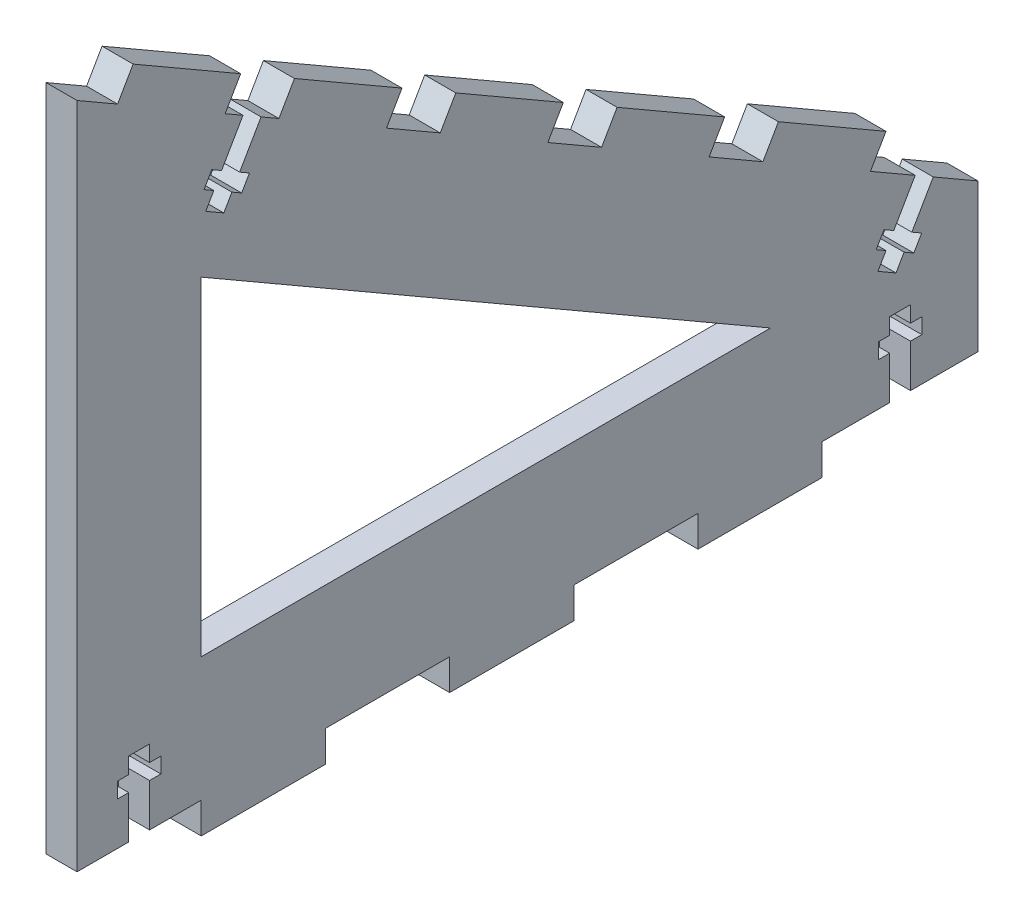
SolidWorks part; units mm, degrees
ref_plane "Front Plane" through (0, 0, 0) normal (0, 0, 1) x (1, 0, 0)
ref_plane "Top Plane" through (0, 0, 0) normal (0, 1, 0) x (1, 0, 0)
ref_plane "Right Plane" through (0, 0, 0) normal (1, 0, 0) x (0, 0, -1)
sketch "Sketch1" plane through (-32.0384, 0, 0) normal (-1, 0, 0) x (0, 0, 1)
  line L0 (-213.5096, 95.25) -> (-213.5096, 125.4926)
  line L1 (165.3114, 95.25) -> (-69.85, 95.25) construction
  line L2 (-213.5096, 125.4926) -> (-29.2385, 231.8816)
  line L3 (-29.2385, 231.8816) -> (-29.2385, 95.25)
  line L4 (-29.2385, 95.25) -> (-213.5096, 95.25)
  line L5 (-29.2385, 231.8816) -> (-42.2787, 224.3528) construction
  line L6 (-29.2385, 95.25) -> (-29.2385, 231.8816) construction
extrude "Boss-Extrude1" add sketch "Sketch1" along normal mid plane 6.35
sketch "Sketch2" plane through (-35.2134, 0, 0) normal (-1, 0, 0) x (0, 0, 1)
  line L14 (-54.6385, 120.65) -> (-54.6385, 187.8875)
  line L15 (-171.0972, 120.65) -> (-54.6385, 120.65)
  line L16 (-54.6385, 187.8875) -> (-171.0972, 120.65)
  line L17 (-54.6385, 120.65) -> (-54.6385, 187.8875)
  line L18 (-171.0972, 120.65) -> (-54.6385, 120.65)
  line L19 (-54.6385, 187.8875) -> (-171.0972, 120.65)
  dimension "D1" = 25.4
extrude "Cut-Extrude1" cut sketch "Sketch2" against normal blind 6.35
sketch "Sketch3" plane through (0, 186.5718, -107.7173) normal (0, 0.866, -0.5) x (1, 0, 0)
  line L0 (-35.2134, -90.6195) -> (-35.2134, 122.1584) construction
  line L1 (-35.2134, 96.7584) -> (-28.8634, 96.7584)
  line L2 (-35.2134, 96.7584) -> (-35.2134, 71.3584)
  line L3 (-35.2134, 71.3584) -> (-28.8634, 71.3584)
  line L4 (-28.8634, 96.7584) -> (-28.8634, 71.3584)
  line L5 (-28.8634, -90.6195) -> (-28.8634, 122.1584) construction
  dimension "D1" = 25.4
  dimension "D2" = 25.4
extrude "Boss-Extrude2" add sketch "Sketch3" along normal blind 6.35
pattern_linear "LPattern1" count 5 spacing 38.1 along (0, 0.5, 0.866) of "Boss-Extrude2"
sketch "Sketch4" plane through (0, 95.25, 0) normal (0, -1, 0) x (1, 0, 0)
  line L0 (-35.2134, -213.5096) -> (-35.2134, -29.2385) construction
  line L1 (-35.2134, -54.6385) -> (-28.8634, -54.6385)
  line L2 (-35.2134, -54.6385) -> (-35.2134, -80.0385)
  line L3 (-35.2134, -80.0385) -> (-28.8634, -80.0385)
  line L4 (-28.8634, -54.6385) -> (-28.8634, -80.0385)
  line L5 (-28.8634, -213.5096) -> (-28.8634, -29.2385) construction
  dimension "D1" = 25.4
  dimension "D2" = 25.4
extrude "Boss-Extrude3" add sketch "Sketch4" along normal blind 6.35
pattern_linear "LPattern2" count 3 spacing 50.8 along (0, 0, -1) of "Boss-Extrude3"
sketch "Sketch5" plane through (-28.8634, 0, 0) normal (1, 0, 0) x (0, 0, -1)
  line L0 (215.9, 95.25) -> (-165.3114, 95.25) construction
  line L1 (197.5741, 95.25) -> (197.5741, 119.6237) construction
  line L2 (213.5096, 95.25) -> (181.6385, 95.25) construction
  line L3 (41.9385, 95.25) -> (41.9385, 127.2639) construction
  line L4 (54.6385, 95.25) -> (29.2385, 95.25) construction
  line L5 (69.85, 95.25) -> (-165.3114, 95.25) construction
  line B0 (195.4405, 95.25) -> (199.7077, 95.25)
  line B1 (199.7077, 107.188) -> (202.0191, 107.188)
  line B2 (202.0191, 107.188) -> (202.0191, 104.013)
  line B3 (202.0191, 104.013) -> (199.7077, 104.013)
  line B4 (199.7077, 104.013) -> (199.7077, 95.25)
  line B5 (199.7077, 107.188) -> (199.7077, 110.49)
  line B6 (199.7077, 110.49) -> (195.4405, 110.49)
  line B7 (195.4405, 107.188) -> (195.4405, 110.49)
  line B8 (195.4405, 104.013) -> (195.4405, 95.25)
  line B9 (193.1291, 104.013) -> (195.4405, 104.013)
  line B10 (193.1291, 107.188) -> (193.1291, 104.013)
  line B11 (195.4405, 107.188) -> (193.1291, 107.188)
  line B12 (39.8049, 95.25) -> (44.0721, 95.25)
  line B13 (44.0721, 107.188) -> (46.3835, 107.188)
  line B14 (46.3835, 107.188) -> (46.3835, 104.013)
  line B15 (46.3835, 104.013) -> (44.0721, 104.013)
  line B16 (44.0721, 104.013) -> (44.0721, 95.25)
  line B17 (44.0721, 107.188) -> (44.0721, 110.49)
  line B18 (44.0721, 110.49) -> (39.8049, 110.49)
  line B19 (39.8049, 107.188) -> (39.8049, 110.49)
  line B20 (39.8049, 104.013) -> (39.8049, 95.25)
  line B21 (37.4935, 104.013) -> (39.8049, 104.013)
  line B22 (37.4935, 107.188) -> (37.4935, 104.013)
  line B23 (39.8049, 107.188) -> (37.4935, 107.188)
sketch_block_instance "TSlot-1"
sketch_block "TSlot" parameters "D1"=3.302, "D2"=3.175
sketch_block_instance "TSlot-3"
extrude "Cut-Extrude2" cut sketch "Sketch5" against normal blind 6.35
sketch "Sketch6" plane through (-28.8634, 0, 0) normal (1, 0, 0) x (0, 0, -1)
  line L1 (51.2356, 219.1816) -> (73.2326, 206.4816) construction
  line L3 (183.2178, 142.9816) -> (205.2149, 130.2816) construction
  line L4 (202.5111, 131.8426) -> (193.641, 116.4791) construction
  line L5 (191.5126, 138.1926) -> (213.5096, 125.4926) construction
  line L6 (65.0295, 211.2176) -> (57.9097, 198.8857) construction
  line L7 (59.5303, 214.3926) -> (70.5288, 208.0426) construction
  line B0 (204.3588, 130.7758) -> (200.6633, 132.9094)
  line B1 (194.6943, 122.5708) -> (192.6926, 123.7265)
  line B2 (192.6926, 123.7265) -> (194.2801, 126.4761)
  line B3 (194.2801, 126.4761) -> (196.2818, 125.3204)
  line B4 (196.2818, 125.3204) -> (200.6633, 132.9094)
  line B5 (194.6943, 122.5708) -> (193.0433, 119.7112)
  line B6 (193.0433, 119.7112) -> (196.7388, 117.5776)
  line B7 (198.3898, 120.4372) -> (196.7388, 117.5776)
  line B8 (199.9773, 123.1868) -> (204.3588, 130.7758)
  line B9 (201.9791, 122.0311) -> (199.9773, 123.1868)
  line B10 (200.3916, 119.2815) -> (201.9791, 122.0311)
  line B11 (198.3898, 120.4372) -> (200.3916, 119.2815)
  line B12 (66.8773, 210.1508) -> (63.1818, 212.2844)
  line B13 (57.2128, 201.9458) -> (55.2111, 203.1015)
  line B14 (55.2111, 203.1015) -> (56.7986, 205.8511)
  line B15 (56.7986, 205.8511) -> (58.8003, 204.6954)
  line B16 (58.8003, 204.6954) -> (63.1818, 212.2844)
  line B17 (57.2128, 201.9458) -> (55.5618, 199.0862)
  line B18 (55.5618, 199.0862) -> (59.2573, 196.9526)
  line B19 (60.9083, 199.8122) -> (59.2573, 196.9526)
  line B20 (62.4958, 202.5618) -> (66.8773, 210.1508)
  line B21 (64.4975, 201.4061) -> (62.4958, 202.5618)
  line B22 (62.91, 198.6565) -> (64.4975, 201.4061)
  line B23 (60.9083, 199.8122) -> (62.91, 198.6565)
sketch_block_instance "TSlot-4"
sketch_block_instance "TSlot-5"
extrude "Cut-Extrude3" cut sketch "Sketch6" against normal blind 6.35
